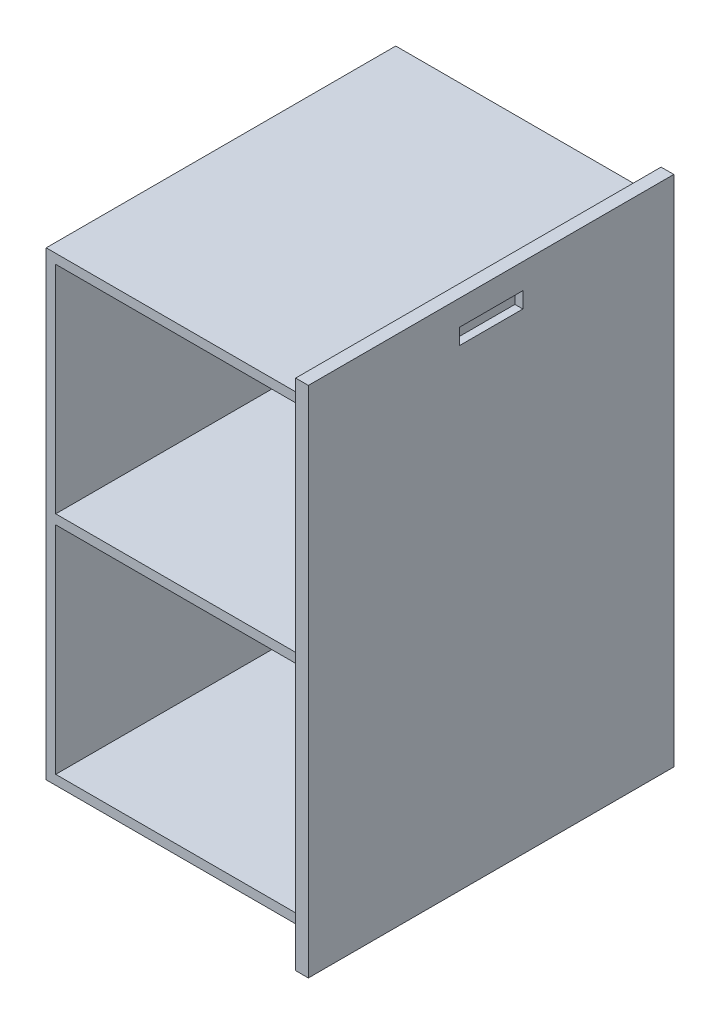
SolidWorks part; units mm, degrees
ref_plane "Front Plane" through (0, 0, 0) normal (0, 0, 1) x (1, 0, 0)
ref_plane "Top Plane" through (0, 0, 0) normal (0, 1, 0) x (1, 0, 0)
ref_plane "Right Plane" through (0, 0, 0) normal (1, 0, 0) x (0, 0, -1)
sketch "Sketch1" plane through (0, 0, 0) normal (0, 0, 1) x (1, 0, 0)
  line L1 (-215.9, -368.3) -> (215.9, -368.3)
  line L2 (-215.9, -368.3) -> (-215.9, 368.3)
  line L3 (-215.9, 368.3) -> (215.9, 368.3)
  line L4 (215.9, -368.3) -> (215.9, 368.3)
  line L5 (200.66, -353.06) -> (-200.66, -353.06)
  line L6 (200.66, -353.06) -> (200.66, 353.06)
  line L7 (200.66, 353.06) -> (-200.66, 353.06)
  line L8 (-200.66, -353.06) -> (-200.66, 353.06)
  line L10 (-200.66, -7.62) -> (200.66, -7.62)
  line L11 (-200.66, -7.62) -> (-200.66, 7.62)
  line L12 (-200.66, 7.62) -> (200.66, 7.62)
  line L13 (200.66, -7.62) -> (200.66, 7.62)
  point P0 (0, 0)
  point P6 (0, 0)
  point P13 (0, 0)
  dimension "D1" = 736.6
  dimension "D2" = 431.8
  dimension "D3" = 15.24
  dimension "D4" = 15.24
  dimension "D5" = 15.24
  dimension "D6" = 15.24
  dimension "D7" = 15.24
extrude "Boss-Extrude1" add sketch "Sketch1" along normal blind 558.8 contours L1 L4 L3 L2 L5 L8 L7 L6 | L12 L8 L10 L6 region at (-207.3617, 0, 0) region at (0, 0, 0)
sketch "Sketch3" plane through (215.9, 0, 0) normal (1, 0, 0) x (0, 0, -1)
  line L1 (-571.5, -420.37) -> (12.7, -420.37)
  line L2 (-571.5, -420.37) -> (-571.5, 400.05)
  line L3 (-571.5, 400.05) -> (12.7, 400.05)
  line L4 (12.7, -420.37) -> (12.7, 400.05)
  line L5 (-279.4, 400.05) -> (-279.4, -439.0322) construction
  point P0 (-279.4, 0)
  dimension "D1" = 292.1
  dimension "D3" = 820.42
  dimension "D4" = 584.2
extrude "Boss-Extrude2" add sketch "Sketch3" against normal blind 20.32
sketch "Sketch4" plane through (215.9, 0, 0) normal (1, 0, 0) x (0, 0, -1)
  line L0 (-571.5, 400.05) -> (-571.5, -420.37) construction
  line L1 (-330.2, 334.3879) -> (-228.6, 334.3879)
  line L2 (-330.2, 334.3879) -> (-330.2, 359.7879)
  line L3 (-330.2, 359.7879) -> (-228.6, 359.7879)
  line L4 (-228.6, 334.3879) -> (-228.6, 359.7879)
  line L5 (-330.2, 334.3879) -> (-228.6, 359.7879) construction
  line L6 (-330.2, 359.7879) -> (-228.6, 334.3879) construction
  point P0 (-279.4, 347.0879)
  dimension "D1" = 101.6
  dimension "D2" = 292.1
  dimension "D3" = 25.4
extrude "Cut-Extrude1" cut sketch "Sketch4" against normal blind 12.7
sketch "Sketch5" plane through (0, 359.7879, 0) normal (0, -1, 0) x (1, 0, 0)
  line L0 (203.2, 228.6) -> (215.9, 228.6) construction
  line L1 (211.571, 330.2) -> (207.2421, 330.2)
  line L3 (211.571, 228.6) -> (207.2421, 228.6)
  line L6 (211.571, 330.2) -> (203.2, 330.2)
  line L7 (211.571, 330.2) -> (211.571, 228.6)
  line L8 (211.571, 228.6) -> (203.2, 228.6)
  line L9 (203.2, 330.2) -> (203.2, 228.6)
  line M2 (215.9, 330.2) -> (203.2, 330.2)
  line M3 (203.2, 330.2) -> (203.2, 228.6)
  line M4 (203.2, 228.6) -> (215.9, 228.6)
extrude "Cut-Extrude2" cut sketch "Sketch5" against normal blind 7.62 contours L7 M2 M3 M4 region at (207.3855, 359.7879, 279.4)
fillet "Fillet1" radius 7.46 1 edges at (211.571, 359.7879, 279.4)
fillet "Fillet2" radius 2.54 1 edges at (211.571, 367.4079, 279.4)
sketch "Sketch6" plane through (-215.9, 0, 0) normal (-1, 0, 0) x (0, 0, 1)
  line L0 (279.4, 368.3) -> (279.4, -368.3) construction
  line L1 (558.8, 368.3) -> (0, 368.3) construction
  line L2 (558.8, -368.3) -> (0, -368.3) construction
  circle A0 centre (441.6858, 330.962) radius 2.54
  circle A1 centre (401.5538, 330.962) radius 2.54
  circle A2 centre (421.6198, 315.976) radius 2.54
  circle A3 centre (137.1802, 315.976) radius 2.54
  circle A4 centre (157.2462, 330.962) radius 2.54
  circle A5 centre (117.1142, 330.962) radius 2.54
  dimension "D2" = 5.08
  dimension "D4" = 5.08
  dimension "D5" = 40.132
  dimension "D6" = 5.08
  dimension "D7" = 20.066
  dimension "D8" = 20.066
  dimension "D1" = 14.986
  dimension "D3" = 37.338
extrude "Cut-Extrude3" cut sketch "Sketch6" against normal blind 9.906
ref_plane "Plane1" through (-215.9, 368.3, 558.8) normal (1, 0, 0) x (0, 0, -1)
sketch "Sketch9" plane through (0, 368.3, 0) normal (0, 1, 0) x (1, 0, 0)
  line L0 (-215.9, -279.4) -> (195.58, -279.4) construction
  line L1 (-215.9, -558.8) -> (-215.9, 0) construction
  line L2 (195.58, 12.7) -> (195.58, -571.5) construction
